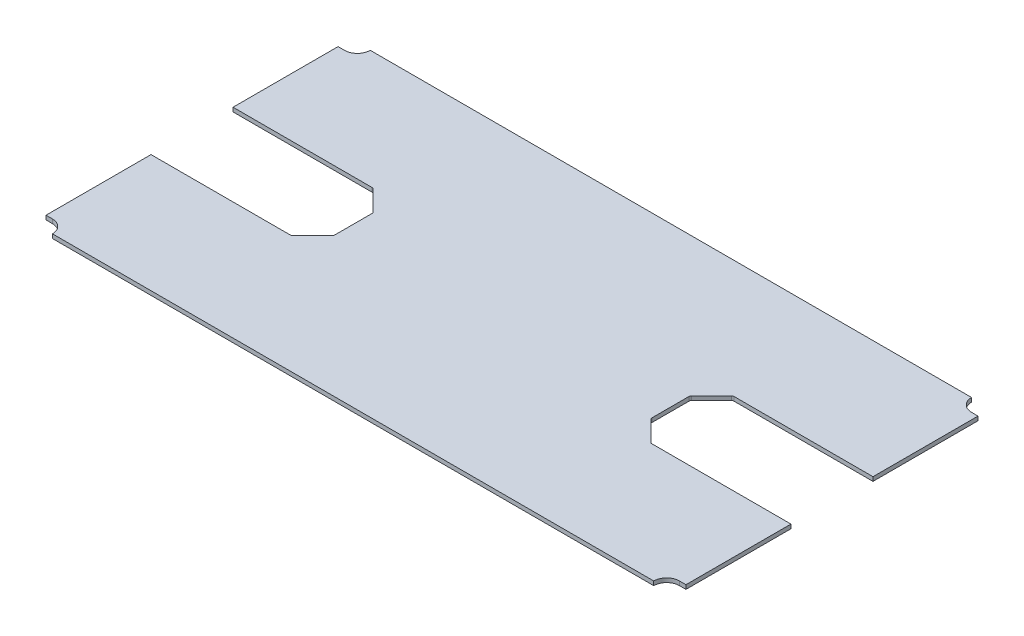
SolidWorks part; units mm, degrees
material "Mahogany"
ref_plane "Front Plane" through (0, 0, 0) normal (0, 0, 1) x (1, 0, 0)
ref_plane "Top Plane" through (0, 0, 0) normal (0, 1, 0) x (1, 0, 0)
ref_plane "Right Plane" through (0, 0, 0) normal (1, 0, 0) x (0, 0, -1)
sketch "Sketch1" plane through (0, 0, 0) normal (0, 1, 0) x (1, 0, 0)
  line L0 (-745, 95.5) -> (-369, 95.5)
  line L1 (-745, 370) -> (745, 370)
  line L2 (-745, 370) -> (-745, -370)
  line L3 (-745, -370) -> (745, -370)
  line L4 (745, 370) -> (745, -370)
  line L5 (-745, 370) -> (745, -370) construction
  line L6 (-745, -370) -> (745, 370) construction
  line L23 (-369, 95.5) -> (-369, -95.5)
  line L24 (-369, -95.5) -> (-745, -95.5)
  line L25 (745, 95.5) -> (369, 95.5)
  line L26 (369, 95.5) -> (369, -95.5)
  line L27 (369, -95.5) -> (745, -95.5)
  line L28 (-745, 340) -> (-730, 340)
  line L29 (0, -370) -> (0, 370) construction
  line L30 (-745, 0) -> (745, 0) construction
  line L31 (-745, -340) -> (-730, -340)
  line L32 (745, 340) -> (730, 340)
  line L33 (745, -340) -> (730, -340)
  arc A0 (-730, 340) -> (-700, 370) centre (-730, 370) ccw
  arc A1 (-730, -340) -> (-700, -370) centre (-730, -370) cw
  arc A2 (730, 340) -> (700, 370) centre (730, 370) cw
  arc A3 (730, -340) -> (700, -370) centre (730, -370) ccw
  point P0 (0, 0)
  point P26 (369, 0)
  point P27 (-369, 0)
  dimension "D6" = 30
  dimension "D4" = 376
  dimension "D5" = 191
  dimension "D2" = 740
  dimension "D1" = 1490
  dimension "D3" = 15
extrude "Boss-Extrude1" add sketch "Sketch1" along normal blind 9.525 contours L27 L26 L25 L4 L1 L2 L0 L23 L24 L3 region at (0, 0, 0)
chamfer "Chamfer1" distance 50 angle 45 4 edges at (369, 4.7625, 95.5) (369, 4.7625, -95.5) (-369, 4.7625, 95.5) (-369, 4.7625, -95.5)
fillet "Fillet2" radius 5 8 edges at (369, 4.7625, -45.5) (369, 4.7625, 45.5) (419, 4.7625, 95.5) (419, 4.7625, -95.5) (-419, 4.7625, 95.5) (-369, 4.7625, 45.5) (-369, 4.7625, -45.5) (-419, 4.7625, -95.5)
equation "\"W\"= 1500"
equation "\"L\"= 780"
equation "\"H\"= 780"
equation "\"ARM_BOLT_SPACING\"= 166"
equation "\"ARM_TO_WALL\"= 200"
equation "\"D4@Sketch1\"=\"ARM_TO_WALL\"+\"ARM_BOLT_SPACING\"+10"
equation "\"D5@Sketch1\"=\"ARM_BOLT_SPACING\"+25"
equation "\"D2@Sketch1\"=\"L\"-40"
equation "\"D1@Sketch1\"=\"W\"-10"
